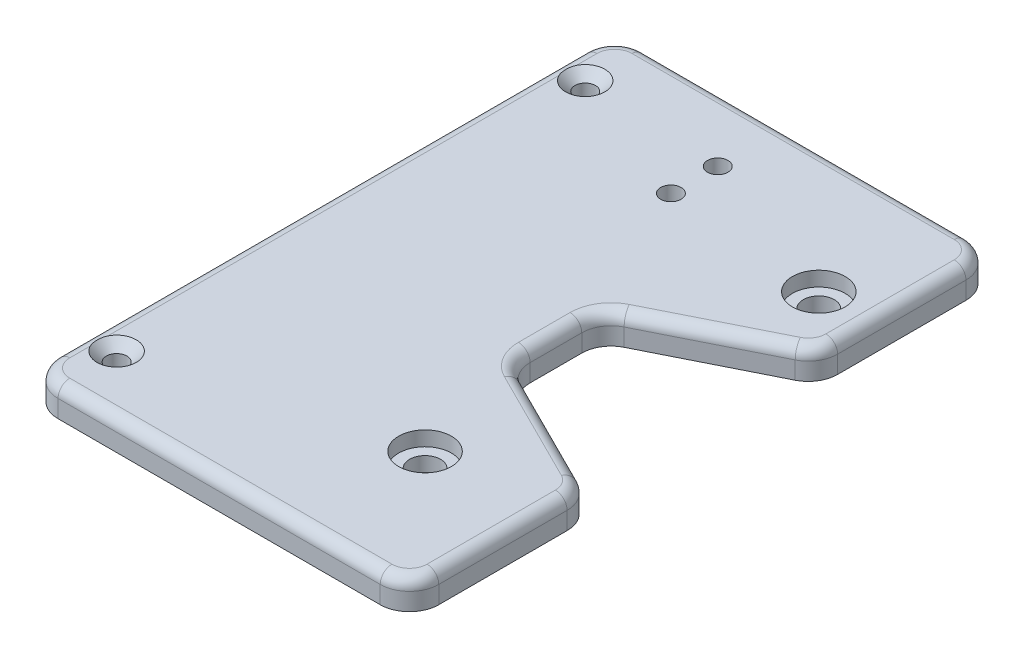
SolidWorks part; units mm, degrees
ref_plane "Front Plane" through (0, 0, 0) normal (0, 0, 1) x (1, 0, 0)
ref_plane "Top Plane" through (0, 0, 0) normal (0, 1, 0) x (1, 0, 0)
ref_plane "Right Plane" through (0, 0, 0) normal (1, 0, 0) x (0, 0, -1)
sketch "Sketch2" plane through (0, 0, 0) normal (0, 1, 0) x (1, 0, 0)
  line L1 (-32.5, 50) -> (32.5, 50)
  line L2 (-32.5, 50) -> (-32.5, -50)
  line L3 (-32.5, -50) -> (32.5, -50)
  line L4 (32.5, 50) -> (32.5, -50)
  line L5 (-32.5, 50) -> (32.5, -50) construction
  line L6 (-32.5, -50) -> (32.5, 50) construction
  circle A0 centre (-27.5, 40) radius 1.75
  circle A1 centre (-27.5, -40) radius 1.75
  circle A2 centre (23.6525, 28.725) radius 2.65
  circle A3 centre (13.65, -28.4925) radius 2.65
  circle A4 centre (23.6525, 28.725) radius 2.5 construction
  circle A5 centre (13.65, -28.4925) radius 2.5 construction
  point P0 (0, 0)
  dimension "D3" = 3.5
  dimension "D4" = 5
  dimension "D8" = 5.3
  dimension "D9" = 5.3
  dimension "D1" = 65
  dimension "D2" = 100
  dimension "D5" = 5
  dimension "D6" = 10
  dimension "D7" = 10
extrude "Boss-Extrude1" add sketch "Sketch2" along normal blind 5
sketch "Sketch3" plane through (0, 5, 0) normal (0, 1, 0) x (1, 0, 0)
  circle A0 centre (23.6525, 28.725) radius 4.5
  circle A1 centre (13.65, -28.4925) radius 4.5
  dimension "D1" = 9
  dimension "D2" = 9
extrude "Cut-Extrude1" cut sketch "Sketch3" against normal blind 2.5
sketch "Sketch4" plane through (0, 5, 0) normal (0, 1, 0) x (1, 0, 0)
  line L5 (7.5, 7.5) -> (7.5, -7.5)
  line L6 (7.5, -7.5) -> (32.5, -20)
  line L7 (32.5, -50) -> (32.5, 50) construction
  line L8 (32.5, -20) -> (32.5, 20)
  line L9 (32.5, 20) -> (7.5, 7.5)
  point P6 (7.5, 0)
  point P7 (32.5, 0)
  dimension "D1" = 40
  dimension "D2" = 25
  dimension "D3" = 15
extrude "Cut-Extrude2" cut sketch "Sketch4" against normal through all
sketch "Sketch5" plane through (0, 5, 0) normal (0, 1, 0) x (1, 0, 0)
  line L0 (-3.5079, 38.632) -> (-3.5079, 30.632) construction
  circle A0 centre (-3.5079, 38.632) radius 1.75
  circle A1 centre (-3.5079, 30.632) radius 1.75
  point P4 (-3.5079, 41.1939)
  dimension "D1" = 3.5
  dimension "D2" = 8
fillet "Fillet1" radius 5 4 edges at (32.5, 2.5, 50) (-32.5, 2.5, -50) (32.5, 2.5, -50) (-32.5, 2.5, 50)
chamfer "Chamfer1" distance 1.6 angle 45 2 edges at (-27.5, 5, 41.75) (-27.5, 5, -38.25)
fillet "Fillet3" radius 5 4 edges at (32.5, 2.5, -20) (32.5, 2.5, 20) (7.5, 2.5, 7.5) (7.5, 2.5, -7.5)
fillet "Fillet2" radius 2 16 edges at (-31.0355, 5, 48.5355) (-32.5, 5, 0) (-31.0355, 5, -48.5355) (0, 5, -50) (31.0355, 5, -48.5355) (32.5, 5, -34.0451) (32.5, 5, 34.0451) (31.0355, 5, 48.5355) (0, 5, 50) (7.5, 5, 0) (31.7533, 5, -20.4615) (20, 5, -13.75) (8.2467, 5, -7.0385) (8.2467, 5, 7.0385) (20, 5, 13.75) (31.7533, 5, 20.4615)
extrude "Cut-Extrude3" cut sketch "Sketch5" against normal through all
